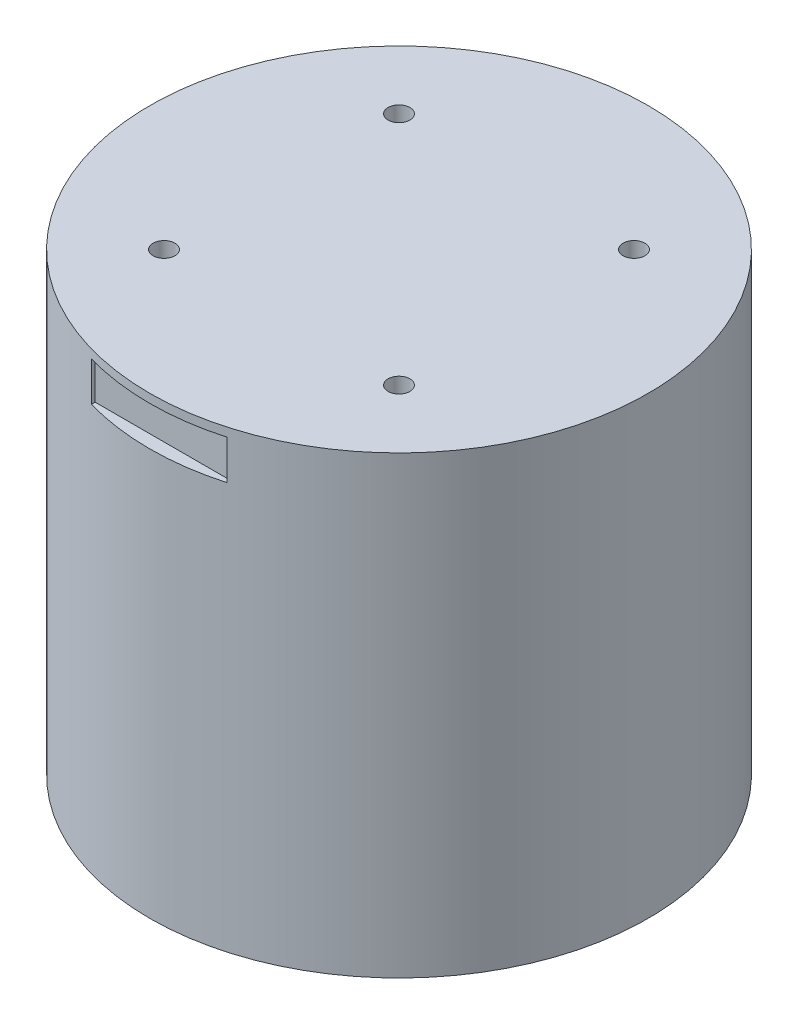
SolidWorks part; units mm, degrees
ref_plane "前视基准面" through (0, 0, 0) normal (0, 0, 1) x (1, 0, 0)
ref_plane "上视基准面" through (0, 0, 0) normal (0, 1, 0) x (1, 0, 0)
ref_plane "右视基准面" through (0, 0, 0) normal (1, 0, 0) x (0, 0, -1)
other "Configuration Table"
sketch "草图1" plane through (0, 0, 0) normal (0, 1, 0) x (1, 0, 0)
  circle A0 centre (0, 0) radius 28.5
  dimension "D1" = 57
extrude "凸台-拉伸1" add sketch "草图1" along normal blind 52
sketch "草图2" plane through (0, 0, 0) normal (0, -1, 0) x (1, 0, 0)
  circle A0 centre (0, 0) radius 17.5
  dimension "D1" = 35
extrude "凸台-拉伸2" add sketch "草图2" along normal blind 1
sketch "草图3" plane through (0, -1, 0) normal (0, -1, 0) x (1, 0, 0)
  circle A0 centre (0, 0) radius 13.5 construction
  circle A1 centre (0, 13.5) radius 1.25
  circle A2 centre (11.6913, 6.75) radius 1.25
  circle A3 centre (11.6913, -6.75) radius 1.25
  circle A4 centre (0, -13.5) radius 1.25
  circle A5 centre (-11.6913, -6.75) radius 1.25
  circle A6 centre (-11.6913, 6.75) radius 1.25
  circle A7 centre (0, 0) radius 4.75
  point P18 (0, 0)
  dimension "D1" = 27
  dimension "D2" = 2.5
  dimension "D4" = 9.5
  dimension "D3" = 6
extrude "切除-拉伸1" cut sketch "草图3" against normal blind 3.5
cosmetic thread "装饰螺纹线2"
cosmetic thread "装饰螺纹线3"
cosmetic thread "装饰螺纹线7"
cosmetic thread "装饰螺纹线8"
cosmetic thread "装饰螺纹线9"
cosmetic thread "装饰螺纹线10"
other "移动面1" flip direction yes face at (11.6913, 2.5, -8) face at (0, 2.5, -14.75) face at (-11.6913, 2.5, -8) face at (-11.6913, 2.5, 5.5) face at (0, 2.5, 12.25) face at (11.6913, 2.5, 5.5) offset 3.5 parameters "D1"=3.5
sketch "草图4" plane through (0, 0, 0) normal (0, -1, 0) x (1, 0, 0)
  circle A0 centre (0, 0) radius 25 construction
  circle A1 centre (0, 25) radius 1.25
  circle A2 centre (21.6506, 12.5) radius 1.25
  circle A3 centre (21.6506, -12.5) radius 1.25
  circle A4 centre (0, -25) radius 1.25
  circle A5 centre (-21.6506, -12.5) radius 1.25
  circle A6 centre (-21.6506, 12.5) radius 1.25
  point P18 (0, 0)
  dimension "D1" = 50
  dimension "D2" = 2.5
  dimension "D3" = 6
extrude "切除-拉伸2" cut sketch "草图4" against normal blind 5
cosmetic thread "装饰螺纹线1"
cosmetic thread "装饰螺纹线4"
cosmetic thread "装饰螺纹线5"
cosmetic thread "装饰螺纹线6"
cosmetic thread "装饰螺纹线11"
cosmetic thread "装饰螺纹线12"
ref_plane "基准面1" through (0, 0, 28.5) normal (0, 0, 1) x (1, 0, 0)
sketch "草图5" plane through (0, 0, 28.5) normal (0, 0, 1) x (1, 0, 0)
  line L0 (28.5, 52) -> (-28.5, 52) construction
  line L1 (-7.75, 46.5) -> (7.75, 46.5)
  line L2 (-7.75, 46.5) -> (-7.75, 51)
  line L3 (-7.75, 51) -> (7.75, 51)
  line L4 (7.75, 46.5) -> (7.75, 51)
  line L5 (-7.75, 46.5) -> (7.75, 51) construction
  line L6 (-7.75, 51) -> (7.75, 46.5) construction
  point P0 (0, 48.75)
  dimension "D1" = 15.5
  dimension "D2" = 4.5
  dimension "D3" = 1
extrude "切除-拉伸3" cut sketch "草图5" against normal blind 1.5
sketch "草图6" plane through (0, 52, 0) normal (0, 1, 0) x (1, 0, 0)
  line L1 (-13.435, -13.435) -> (13.435, -13.435) construction
  line L2 (-13.435, -13.435) -> (-13.435, 13.435) construction
  line L3 (-13.435, 13.435) -> (13.435, 13.435) construction
  line L4 (13.435, -13.435) -> (13.435, 13.435) construction
  line L5 (-13.435, -13.435) -> (13.435, 13.435) construction
  line L6 (-13.435, 13.435) -> (13.435, -13.435) construction
  circle A0 centre (13.435, 13.435) radius 1.25
  circle A1 centre (13.435, -13.435) radius 1.25
  circle A2 centre (-13.435, -13.435) radius 1.25
  circle A3 centre (-13.435, 13.435) radius 1.25
  point P0 (0, 0)
  point P15 (0, 0)
  dimension "D1" = 38
  dimension "D2" = 2.5
  dimension "D3" = 4
extrude "切除-拉伸4" cut sketch "草图6" against normal blind 5
cosmetic thread "装饰螺纹线13"
cosmetic thread "装饰螺纹线14"
cosmetic thread "装饰螺纹线15"
cosmetic thread "装饰螺纹线16"
ref_axis "基准轴1" through (0, 2.5, 0) along (0, -1, 0)
ref_plane "基准面2" through (0, 0, 0) normal (-0.7071, 0, 0.7071) x (0, -1, 0)
